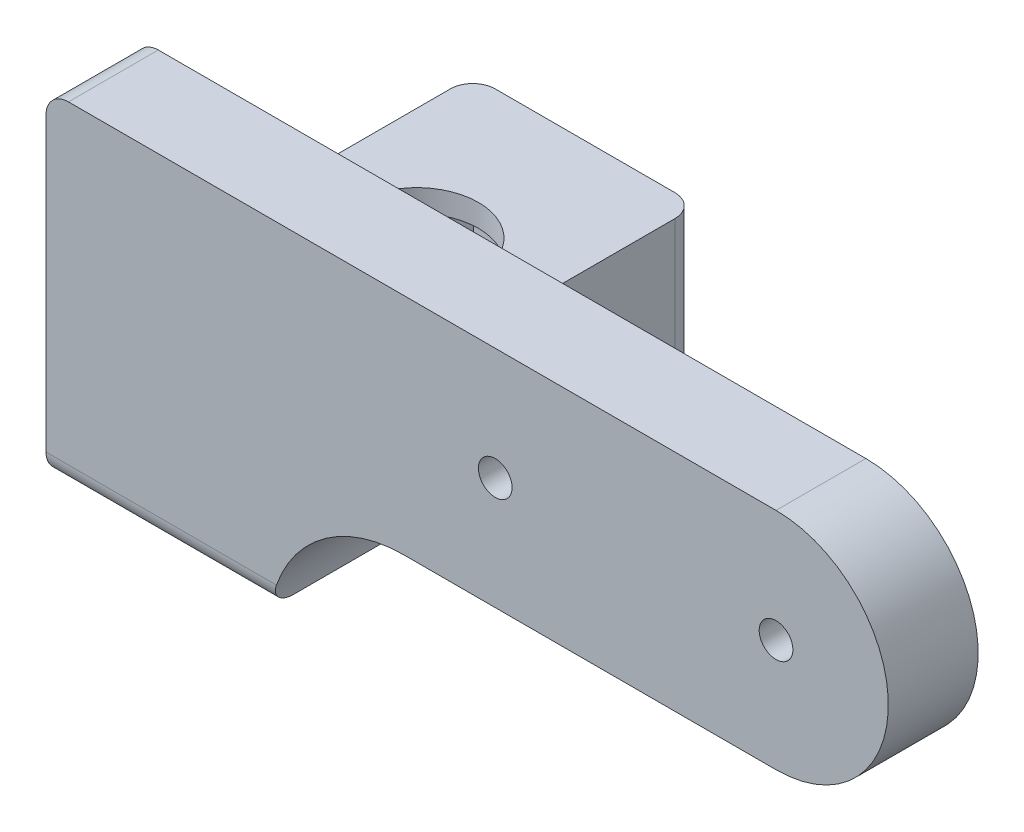
SolidWorks part; units mm, degrees
ref_plane "Front Plane" through (0, 0, 0) normal (0, 0, 1) x (1, 0, 0)
ref_plane "Top Plane" through (0, 0, 0) normal (0, 1, 0) x (1, 0, 0)
ref_plane "Right Plane" through (0, 0, 0) normal (1, 0, 0) x (0, 0, -1)
sketch "Sketch1" plane through (0, 0, 0) normal (0, 0, 1) x (1, 0, 0)
  line L1 (-25, 10) -> (40, 10)
  line L2 (-25, 10) -> (-25, -10)
  line L3 (-25, -10) -> (40, -10)
  arc A0 (40, -10) -> (40, 10) centre (40, 0) ccw
  dimension "D5" = 20
  dimension "D1" = 20
  dimension "D2" = 10
  dimension "D3" = 65
  dimension "D4" = 25
extrude "Boss-Extrude1" add sketch "Sketch1" along normal blind 8
sketch "Sketch2" plane through (0, 0, 8) normal (0, 0, 1) x (1, 0, 0)
  line L0 (40, 10) -> (-25, 10) construction
  circle A1 centre (40, 0) radius 1.5
  dimension "D2" = 3
  dimension "D1" = 10
  dimension "D3" = 40
extrude "Cut-Extrude1" cut sketch "Sketch2" against normal blind 10
sketch "Sketch3" plane through (0, 0, 0) normal (0, 0, -1) x (-1, 0, 0)
  line L0 (-40, 10) -> (25, 10) construction
  circle A1 centre (-15, 0) radius 1.5
  dimension "D2" = 3
  dimension "D1" = 10
  dimension "D3" = 15
extrude "Cut-Extrude2" cut sketch "Sketch3" against normal blind 10
sketch "Sketch6" plane through (0, 0, 0) normal (0, 0, -1) x (-1, 0, 0)
  line L1 (25, -10) -> (5, -10)
  line L2 (25, -10) -> (25, -20)
  line L3 (25, -20) -> (5, -20)
  line L4 (5, -10) -> (5, -20)
  dimension "D1" = 20
  dimension "D2" = 10
extrude "Boss-Extrude3" add sketch "Sketch6" along normal blind 30 and the other way blind 8
fillet "Fillet3" radius 12 1 edges at (-5, -10, 4)
sketch "Sketch7" plane through (0, -10, 0) normal (0, 1, 0) x (1, 0, 0)
  line L1 (-5, 30) -> (-25, 30)
  line L2 (-5, 30) -> (-5, 0)
  line L3 (-5, 0) -> (-25, 0)
  line L4 (-25, 30) -> (-25, 0)
extrude "Boss-Extrude4" add sketch "Sketch7" along normal blind 2
sketch "Sketch8" plane through (0, -20, 0) normal (0, -1, 0) x (1, 0, 0)
  line L1 (-5, 8) -> (-25, 8) construction
  line L2 (-5, 0) -> (-5, -30) construction
  line L4 (-12.0928, -7.0126) -> (-20.4637, -8.4886)
  line L15 (-20.4637, -8.4886) -> (-23.3709, -16.476)
  line L16 (-23.3709, -16.476) -> (-17.9072, -22.9874)
  line L17 (-17.9072, -22.9874) -> (-9.5363, -21.5114)
  line L18 (-9.5363, -21.5114) -> (-6.6291, -13.524)
  line L19 (-6.6291, -13.524) -> (-12.0928, -7.0126)
  dimension "D2" = 8.5
  dimension "D3" = 1.6291
  dimension "D1" = 15.0126
extrude "Cut-Extrude3" cut sketch "Sketch8" against normal blind 10
sketch "Sketch9" plane through (0, -10, 0) normal (0, -1, 0) x (1, 0, 0)
  line L0 (-20.4637, -8.4886) -> (-9.5363, -21.5114) construction
  line L1 (-12.0928, -7.0126) -> (-17.9072, -22.9874) construction
  line L2 (16.927, -11) -> (16.927, -10.0428) construction
  circle A0 centre (-15, -15) radius 5.5
  dimension "D1" = 11
extrude "Cut-Extrude4" cut sketch "Sketch9" against normal blind 10
fillet "Fillet4" radius 5 2 edges at (-5, -14, 0) (-15, -8, 0)
fillet "Fillet5" radius 2 4 edges at (-15, -20, 8) (-25, 10, 4) (-5, -14, -30) (-25, -14, -30)
